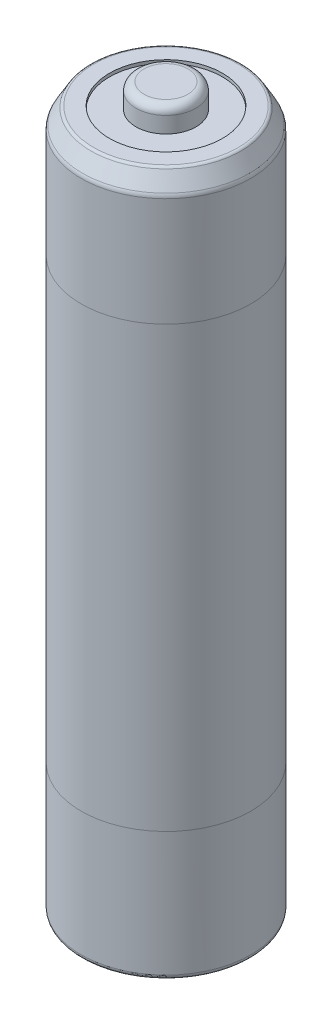
SolidWorks part; units mm, degrees
ref_plane "Plan de face" through (0, 0, 0) normal (0, 0, 1) x (1, 0, 0)
ref_plane "Plan de dessus" through (0, 0, 0) normal (0, 1, 0) x (1, 0, 0)
ref_plane "Plan de droite" through (0, 0, 0) normal (1, 0, 0) x (0, 0, -1)
ref_axis "Axe1" through (0, 0, 0) along (0, 1, 0)
sketch "Esquisse1" plane through (0, 0, 0) normal (0, 0, 1) x (1, 0, 0)
  line L0 (0, 0) -> (0, 74.7809) construction
  line L1 (-1.36, 44.5) -> (0, 44.5)
  line L2 (0, 0) -> (-4.95, 0)
  line L3 (0, 0) -> (0, 44.5)
  line L4 (-4.65, 43.1) -> (-5.183, 42.1768)
  line L5 (-5.25, 0.3) -> (-5.25, 41.9268)
  line L6 (-1.86, 44) -> (-1.86, 43)
  line L12 (-3.5, 43) -> (-1.86, 43)
  line L13 (-3.5, 43.2) -> (-3.5, 43)
  line L15 (-3.5, 43.2) -> (-4.4768, 43.2)
  arc A0 (-1.86, 44) -> (-1.36, 44.5) centre (-1.36, 44) cw
  arc A1 (-5.25, 0.3) -> (-4.95, 0) centre (-4.95, 0.3) ccw
  arc A2 (-4.4768, 43.2) -> (-4.65, 43.1) centre (-4.4768, 43) ccw
  arc A3 (-5.25, 41.9268) -> (-5.183, 42.1768) centre (-4.75, 41.9268) cw
  dimension "D5" = 0.5
  dimension "D6" = 0.2
  dimension "D13" = 0.3
  dimension "D7" = 0.5
  dimension "D1" = 10.5
  dimension "D2" = 43.2
  dimension "D3" = 44.5
  dimension "D4" = 3.72
  dimension "D8" = 30
  dimension "D9" = 9.3
  dimension "D14" = 7
  dimension "D15" = 0.2
revolve "Révolution1" add sketch "Esquisse1" angle 360 about L0
sketch "Esquisse2" plane through (0, 0, 0) normal (0, 0, 1) x (1, 0, 0)
  line L0 (-5.25, 8) -> (5.25, 8)
  line L1 (-5.25, 41.9268) -> (-5.25, 0.3) construction
  line L2 (5.25, 0.3) -> (5.25, 41.9268) construction
  line L3 (-5.25, 35.2) -> (5.25, 35.2)
  line L4 (-5.25, 41.9268) -> (-5.25, 0.3) construction
  line L5 (3.5, 43.2) -> (-3.5, 43.2) construction
  line L7 (5.25, 0.3) -> (5.25, 41.9268) construction
  dimension "D1" = 8
  dimension "D2" = 8
split line "Ligne de séparation1"
